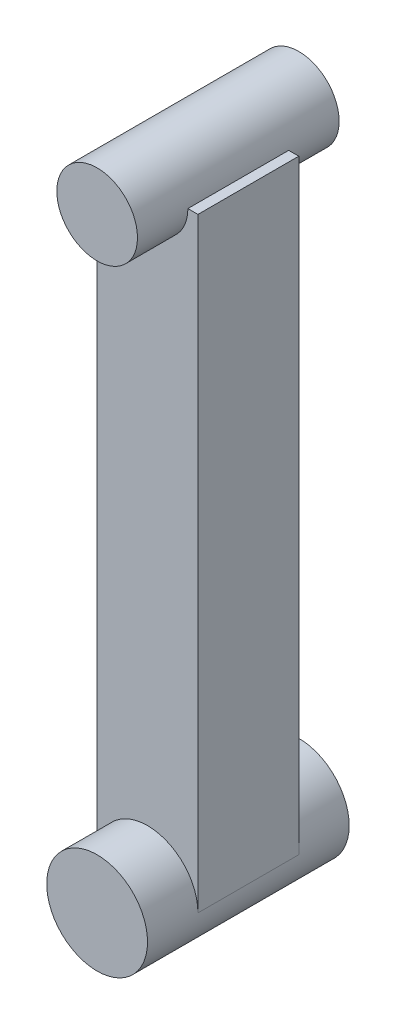
SolidWorks part; units mm, degrees
ref_plane "前视基准面" through (0, 0, 0) normal (0, 0, 1) x (1, 0, 0)
ref_plane "上视基准面" through (0, 0, 0) normal (0, 1, 0) x (1, 0, 0)
ref_plane "右视基准面" through (0, 0, 0) normal (1, 0, 0) x (0, 0, -1)
other "Configuration Table"
sketch "Sketch1" plane through (0, 0, 0) normal (0, 1, 0) x (1, 0, 0)
  line L1 (-15, -15) -> (15, -15)
  line L2 (-15, -15) -> (-15, 15)
  line L3 (-15, 15) -> (15, 15)
  line L4 (15, -15) -> (15, 15)
  line L5 (-15, -15) -> (15, 15) construction
  line L6 (-15, 15) -> (15, -15) construction
  point P0 (0, 0)
extrude "Boss-Extrude1" add sketch "Sketch1" along normal blind 180
sketch "Sketch2" plane through (0, 0, 0) normal (0, 0, 1) x (1, 0, 0)
  line L0 (-15, 180) -> (15, 180) construction
  circle A0 centre (0, 0) radius 15
  circle A1 centre (0, 180) radius 12
extrude "Boss-Extrude2" add sketch "Sketch2" along normal blind 30 and the other way blind 30
sketch3d "3DSketch1"
  line L0 (0, 0, -100) -> (0, 0, 100) construction
ref_axis "Axis_J3" through (0, 0, -100) along (0, 0, 1)
sketch3d "3DSketch2"
  line L0 (0, 180, -100) -> (0, 180, 100) construction
ref_axis "Axis_J4" through (0, 180, -100) along (0, 0, 1)
ref_plane "Mate_Mid" through (0, 0, 0) normal (0, 0, 1) x (1, 0, 0)
